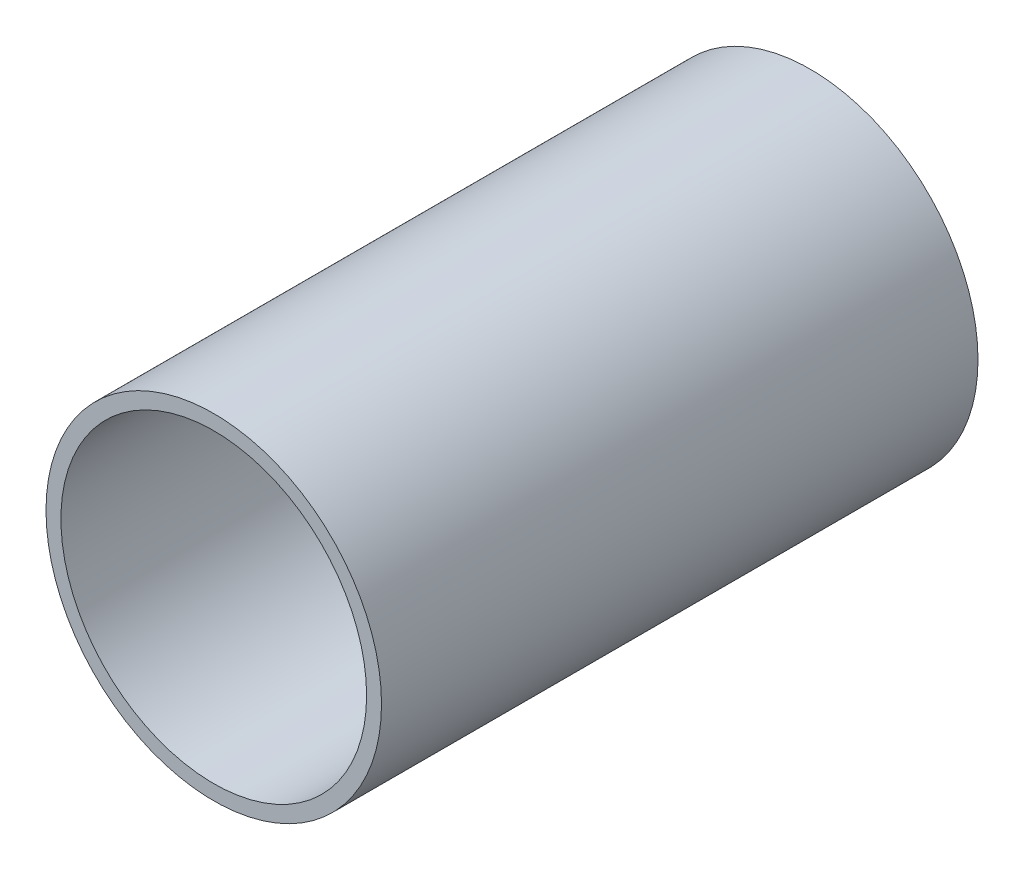
SolidWorks part; units mm, degrees
ref_plane "Front Plane" through (0, 0, 0) normal (0, 0, 1) x (1, 0, 0)
ref_plane "Top Plane" through (0, 0, 0) normal (0, 1, 0) x (1, 0, 0)
ref_plane "Right Plane" through (0, 0, 0) normal (1, 0, 0) x (0, 0, -1)
sketch "Sketch1" plane through (0, 0, 0) normal (0, 0, 1) x (1, 0, 0)
  circle A0 centre (0, 0) radius 22.5
  circle A1 centre (0, 0) radius 20.5
  dimension "D1" = 45
  dimension "D2" = 41
extrude "Boss-Extrude1" add sketch "Sketch1" along normal blind 80
